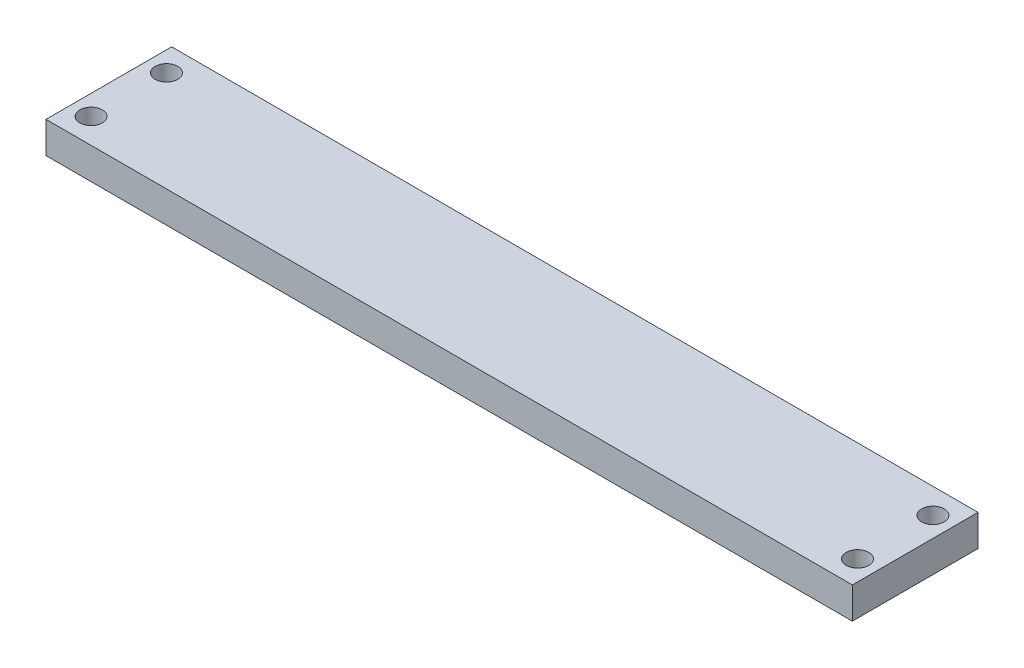
SolidWorks part; units mm, degrees
ref_plane "Front Plane" through (0, 0, 0) normal (0, 0, 1) x (1, 0, 0)
ref_plane "Top Plane" through (0, 0, 0) normal (0, 1, 0) x (1, 0, 0)
ref_plane "Right Plane" through (0, 0, 0) normal (1, 0, 0) x (0, 0, -1)
sketch "Sketch2" plane through (0, 0, 0) normal (0, 1, 0) x (1, 0, 0)
  line L1 (-39.8374, 20.9756) -> (88.5126, 20.9756)
  line L2 (-39.8374, 20.9756) -> (-39.8374, 0.9756)
  line L3 (-39.8374, 0.9756) -> (88.5126, 0.9756)
  line L4 (88.5126, 20.9756) -> (88.5126, 0.9756)
  dimension "D1" = 20
  dimension "D2" = 128.35
extrude "Boss-Extrude1" add sketch "Sketch2" along normal blind 5
sketch "Sketch3" plane through (0, 5, 0) normal (0, 1, 0) x (1, 0, 0)
  line L2 (-39.8374, 20.9756) -> (-39.8374, 0.9756) construction
  line L3 (88.5126, 0.9756) -> (88.5126, 20.9756) construction
  line L4 (-36.6624, 16.9756) -> (-36.6624, 4.9756) construction
  line L6 (-39.8374, 10.9756) -> (-36.6624, 10.9756) construction
  point P0 (-36.6624, 16.9756)
  point P1 (-36.6624, 4.9756)
  point P9 (85.3376, 16.9756)
  point P11 (85.3376, 4.9756)
  dimension "D1" = 12
  dimension "D3" = 3.175
  dimension "D4" = 3.175
  dimension "D5" = 3.175
  dimension "D6" = 122
hole_wizard "M3 Clearance Hole1" positions "Sketch3" profile "Sketch4" hole size "M3" standard "ANSI Metric" end condition through all
sketch "Sketch4" plane through (-36.6624, 5, -16.9756) normal (1, 0, 0) x (0, 0, 1)
  line L0 (0, 0) -> (0, 5)
  line L1 (0, 5) -> (1.8, 5)
  line L2 (1.8, 5) -> (1.8, 0)
  line L5 (1.8, 0) -> (0, 0)
  line L11 (0, -6.35) -> (0, 107.95) construction
  dimension "Thru Hole Dia." = 3.6
  dimension "Thru Hole Depth" = 5
